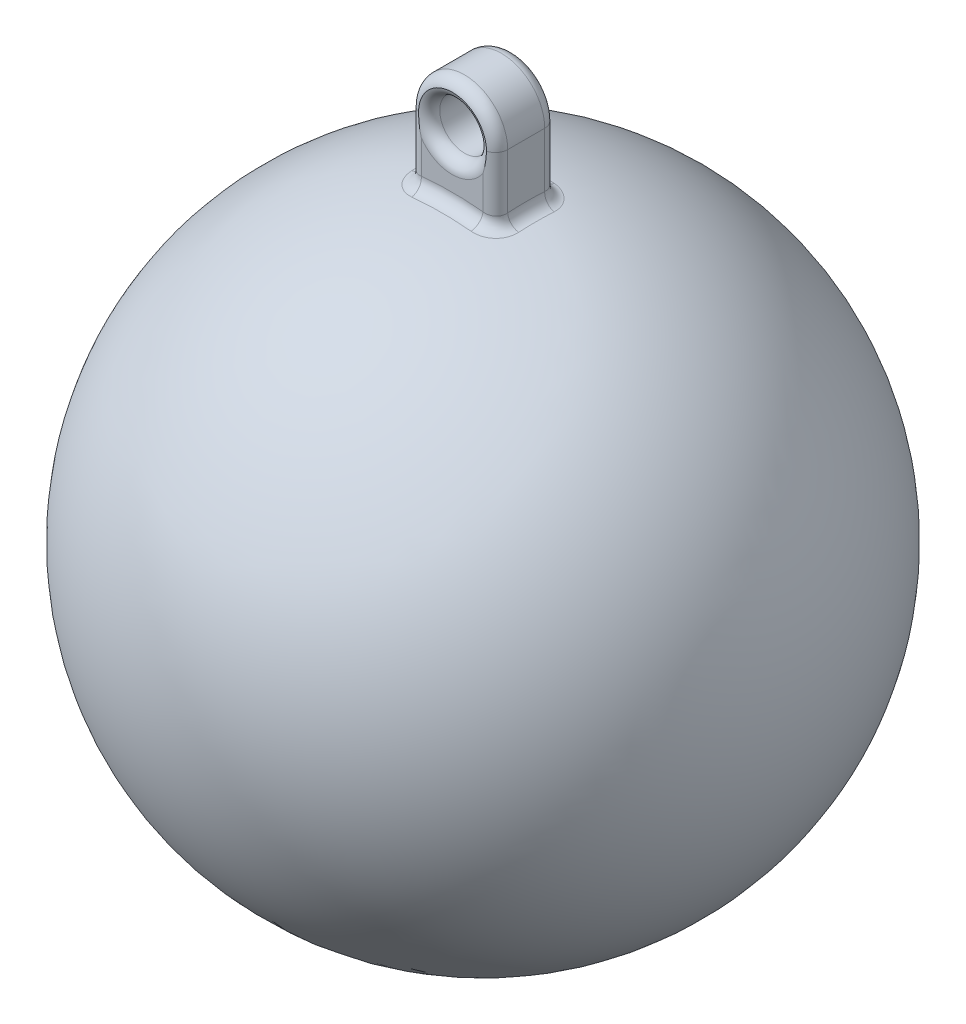
SolidWorks part; units mm, degrees
ref_plane "Front Plane" through (0, 0, 0) normal (0, 0, 1) x (1, 0, 0)
ref_plane "Top Plane" through (0, 0, 0) normal (0, 1, 0) x (1, 0, 0)
ref_plane "Right Plane" through (0, 0, 0) normal (1, 0, 0) x (0, 0, -1)
sketch "Sketch1" plane through (0, 0, 0) normal (0, 1, 0) x (1, 0, 0)
  line L0 (-250, 0) -> (250, 0)
  arc A0 (-250, 0) -> (250, 0) centre (0, 0) ccw
  dimension "D1" = 250
revolve "Revolve1" add sketch "Sketch1" angle 360 about L0
sketch "Sketch2" plane through (0, 0, 0) normal (0, 0, 1) x (1, 0, 0)
  line L0 (0, 0) -> (0, 409.6238) construction
  line L2 (-35, 300) -> (35, 300) construction
  line L3 (-35, 300) -> (-35, 200)
  line L4 (-35, 200) -> (35, 200)
  line L5 (35, 300) -> (35, 200)
  arc A0 (35, 300) -> (-35, 300) centre (0, 300) ccw
  circle A1 centre (0, 300) radius 20
  dimension "D1" = 35
  dimension "D4" = 40
  dimension "D2" = 200
  dimension "D3" = 100
extrude "Boss-Extrude1" add sketch "Sketch2" along normal mid plane 50
fillet "Fillet1" radius 10 12 edges at (35, 247.5379, 0) (-35, 247.5379, 0) (20, 300, -25) (35, 273.1361, -25) (0, 335, -25) (-35, 273.1361, -25) (0, 248.7469, -25) (20, 300, 25) (0, 335, 25) (35, 273.1361, 25) (0, 248.7469, 25) (-35, 273.1361, 25)
